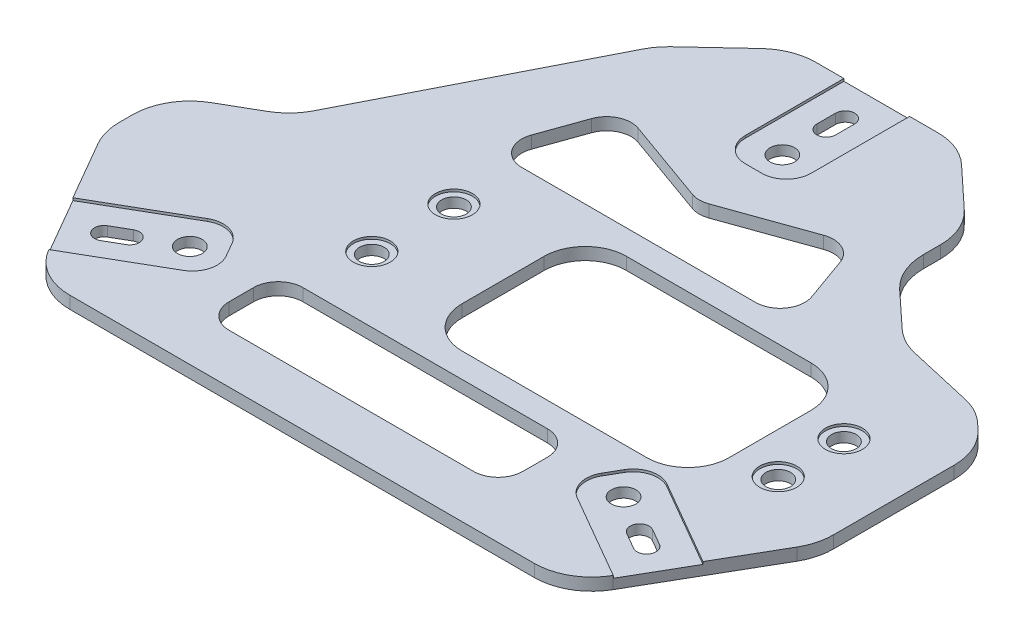
SolidWorks part; units mm, degrees
ref_plane "Front Plane" through (0, 0, 0) normal (0, 0, 1) x (1, 0, 0)
ref_plane "Top Plane" through (0, 0, 0) normal (0, 1, 0) x (1, 0, 0)
ref_plane "Right Plane" through (0, 0, 0) normal (1, 0, 0) x (0, 0, -1)
sketch "Center" plane through (0, 0, 0) normal (0, 1, 0) x (1, 0, 0)
  line L0 (0, 0) -> (0, 30.5)
  line L1 (0, 0) -> (-26.4138, -15.25)
  line L2 (0, 0) -> (26.4138, -15.25)
  line L3 (-30.5, 0) -> (30.5, 0) construction
  circle A0 centre (0, 0) radius 30.5
  dimension "D1" = 61
  dimension "D2" = 120
  dimension "D3" = 120
sketch "Borders" plane through (0, 0, 0) normal (0, 1, 0) x (1, 0, 0)
  line L0 (-43.5, -28) -> (43.5, -28)
  line L1 (-43.5, 42) -> (43.5, 42)
  line L2 (43.5, 42) -> (43.5, -28)
  line L3 (-43.5, 42) -> (-43.5, -28)
  line L4 (0, 30.5) -> (0, 42)
  dimension "D1" = 28
  dimension "D2" = 42
  dimension "D3" = 43.5
  dimension "D4" = 43.5
sketch "Sketch5" plane through (0, 0, 0) normal (0, 1, 0) x (1, 0, 0)
  line L0 (-32.33, -28) -> (32.33, -28)
  line L1 (-43.5, -28) -> (43.5, -28) construction
  line L2 (32.33, -28) -> (43.5, -8.653)
  line L3 (43.5, 42) -> (43.5, -28) construction
  line L4 (43.5, -8.653) -> (43.5, 10.937)
  line L5 (43.5, 10.937) -> (39.1099, 15.1144)
  line L6 (39.1099, 15.1144) -> (27.4118, 17.7893)
  line L7 (27.4118, 17.7893) -> (19.4172, 25.2132)
  line L8 (19.4172, 25.2132) -> (19.4172, 33.3932)
  line L9 (19.4172, 33.3932) -> (10.1875, 42)
  line L10 (-43.5, 42) -> (43.5, 42) construction
  line L11 (10.1875, 42) -> (-10.1875, 42)
  line L12 (-10.1875, 42) -> (-18.7859, 33.9772)
  line L13 (-18.7859, 33.9772) -> (-33.809, 4.4716)
  line L14 (-33.809, 4.4716) -> (-43.5, -1.103)
  line L15 (-43.5, 42) -> (-43.5, -28) construction
  line L16 (-43.5, -1.103) -> (-43.5, -8.653)
  line L17 (-43.5, -8.653) -> (-32.33, -28)
  dimension "D2" = 22.34
  dimension "D3" = 6.06
  dimension "D4" = 12
  dimension "D5" = 10.91
  dimension "D6" = 8.18
  dimension "D7" = 12.62
  dimension "D8" = 11.76
  dimension "D9" = 33.11
  dimension "D10" = 64.66
  dimension "D11" = 7.55
  dimension "D12" = 19.59
  dimension "D13" = 20.375
  dimension "D14" = 11.18
  dimension "D15" = 22.34
  dimension "D16" = 120
  dimension "D17" = 160
  dimension "D18" = 210
  dimension "D19" = 137
extrude "Boss-Extrude1" add sketch "Sketch5" along normal blind 0.75 and the other way blind 0.75
fillet "Fillet_7mm" radius 7 7 edges at (10.1875, 0, -42) (43.5, 0, -10.937) (43.5, 0, 8.653) (32.33, 0, 28) (-32.33, 0, 28) (-43.5, 0, 8.653) (-10.1875, 0, -42)
fillet "Fillet_8mm" radius 7 7 edges at (19.4172, 0, -33.3932) (19.4172, 0, -25.2132) (27.4118, 0, -17.7893) (39.1099, 0, -15.1144) (-43.5, 0, 1.103) (-33.809, 0, -4.4716) (-18.7859, 0, -33.9772)
sketch "Sketch7" plane through (0, 0.75, 0) normal (0, 1, 0) x (1, 0, 0)
  line L0 (0, 0) -> (0.0006, 42) construction
  line L1 (7.4301, 42) -> (-7.4289, 42) construction
  line L2 (-3.9992, 42) -> (-3.9995, 30.0001)
  line L3 (-0.9995, 27) -> (1.0004, 27)
  line L4 (4.0004, 30) -> (4.0004, 42)
  arc A0 (1.0004, 27) -> (4.0004, 30) centre (1.0004, 30) ccw
  arc A1 (-0.9995, 27) -> (-3.9995, 30.0001) centre (-0.9995, 30) cw
  point P11 (4.0004, 27)
  point P14 (-3.9996, 27)
  line M11 (7.4301, 42) -> (-7.4289, 42)
  dimension "D3" = 3
  dimension "D4" = 3
  dimension "D1" = 8
  dimension "D2" = 15
extrude "Grooves" cut sketch "Sketch7" against normal blind 0.3 and the other way through all contours L3 L0 L2 A1 M11 | L0 L3 A0 L4 M11 region at (-1.9552, 0.75, -34.7271) region at (1.9562, 0.75, -34.7271)
sketch "Sketch6" plane through (0, 0.45, 0) normal (0, 1, 0) x (1, 0, 0)
  line L0 (0, 0) -> (0, 30.5)
  line L1 (0, 35.85) -> (0, 38.15)
  line L2 (1.15, 35.85) -> (1.15, 38.15)
  line L3 (-1.15, 35.85) -> (-1.15, 38.15)
  circle A0 centre (0, 0) radius 30.5
  circle A1 centre (0, 0) radius 30.5 construction
  circle A2 centre (0, 30.5) radius 1.5
  arc A3 (1.15, 35.85) -> (-1.15, 35.85) centre (0, 35.85) cw
  arc A4 (1.15, 38.15) -> (-1.15, 38.15) centre (0, 38.15) ccw
  dimension "D1" = 3
  dimension "D2" = 5.35
  dimension "D3" = 2.3
  dimension "D4" = 1.15
  dimension "D5" = 1.15
extrude "CopperRod_Holes" cut sketch "Sketch6" against normal through all contours L2 A4 L3 A3 | A0 A2 | A0 A2 L0 | L0 A2 A0 region at (-0.6315, 0.45, -29.8568) region at (0.6315, 0.45, -29.8568) region at (0, 0.45, -31.1299) region at (0, 0.45, -34.7514)
ref_axis "RotationSymmetrie_CopperRods" through (0, 0.825, 0) along (0, -1, 0)
pattern_circular "CirPattern1" count 3 over 360 about axis through (0, 0.825, 0) along (0, -1, 0) of "Grooves", "CopperRod_Holes"
sketch "Sketch9" plane through (0, 0.75, 0) normal (0, 1, 0) x (1, 0, 0)
  line L0 (-3.5, 10) -> (29, 10)
  line L1 (29, 10) -> (29, -10)
  line L2 (29, -10) -> (-3.5, -10)
  line L3 (-3.5, -10) -> (-3.5, 10)
  line L4 (-3.5, 0) -> (29, 0) construction
  line L5 (0, 42) -> (0, -28) construction
  line L7 (-28.2885, -28) -> (28.2885, -28) construction
  line L8 (-17.895, -17.5) -> (17.895, -17.5) construction
  line L9 (-17.895, -13) -> (17.895, -13)
  line L10 (-17.895, -13) -> (-17.895, -22)
  line L11 (-17.895, -22) -> (17.895, -22)
  line L12 (17.895, -13) -> (17.895, -22)
  line L13 (-18.5, 13) -> (18.5, 13)
  line L14 (18.5, 13) -> (14.1251, 25.2417)
  line L15 (14.1251, 25.2417) -> (0, 20.1937)
  line L16 (0, 20.1937) -> (-14.1251, 25.2417)
  line L17 (-14.1251, 25.2417) -> (-18.5, 13)
  dimension "D1" = 32.5
  dimension "D2" = 20
  dimension "D3" = 3.5
  dimension "D4" = 9
  dimension "D5" = 17.5
  dimension "D6" = 13
  dimension "D7" = 37
  dimension "D8" = 13
  dimension "D9" = 15
  dimension "D10" = 90
  dimension "D11" = 35.79
extrude "Cut-Extrude3" cut sketch "Sketch9" against normal through all
fillet "Fillet_5mm" radius 5 4 edges at (29, 0, 10) (-3.5, 0, 10) (-3.5, 0, -10) (29, 0, -10)
fillet "Fillet_3mm" radius 3 9 edges at (17.895, 0, 22) (-17.895, 0, 22) (-17.895, 0, 13) (17.895, 0, 13) (18.5, 0, -13) (-18.5, 0, -13) (-14.1251, 0, -25.2417) (0, 0, -20.1937) (14.1251, 0, -25.2417)
sketch "Borehole_postion" plane through (0, 0.75, 0) normal (0, 1, 0) x (1, 0, 0)
  line L0 (0, 0) -> (50000, 0) construction
  point P3 (-14.5, 5)
  point P4 (-14.5, -5)
  point P5 (34, 4)
  point P6 (34, -4)
  dimension "D1" = 34
  dimension "D2" = 14.5
  dimension "D3" = 10
  dimension "D4" = 8
hole_wizard "CBORE for M5 Hex Head Bolt1" positions "3DSketch1" profile "Sketch11" counterbore size "M5" standard "ANSI Metric" end condition through all
sketch3d "3DSketch1"
  point P0 (-14.5, 0.75, -5)
  point P3 (-14.5, 0.75, 5)
  point P6 (34, 0.75, -4)
  point P9 (34, 0.75, 4)
sketch "Sketch11" plane through (-14.5, 0.75, -5) normal (1, 0, 0) x (0, 0, 1)
  line L0 (0, 0) -> (0, 1.5)
  line L1 (0, 1.5) -> (1.5, 1.5)
  line L3 (1.5, 1.5) -> (1.5, 0.3)
  line L4 (1.5, 0.3) -> (2.25, 0.3)
  line L5 (2.25, 0.3) -> (2.25, 0)
  line L7 (2.25, 0) -> (0, 0)
  line L11 (0, -6.35) -> (0, 107.95) construction
  dimension "Thru Hole Dia." = 3
  dimension "Thru Hole Depth" = 1.5
  dimension "C'Bore Dia." = 4.5
  dimension "C'Bore Depth" = 0.3
